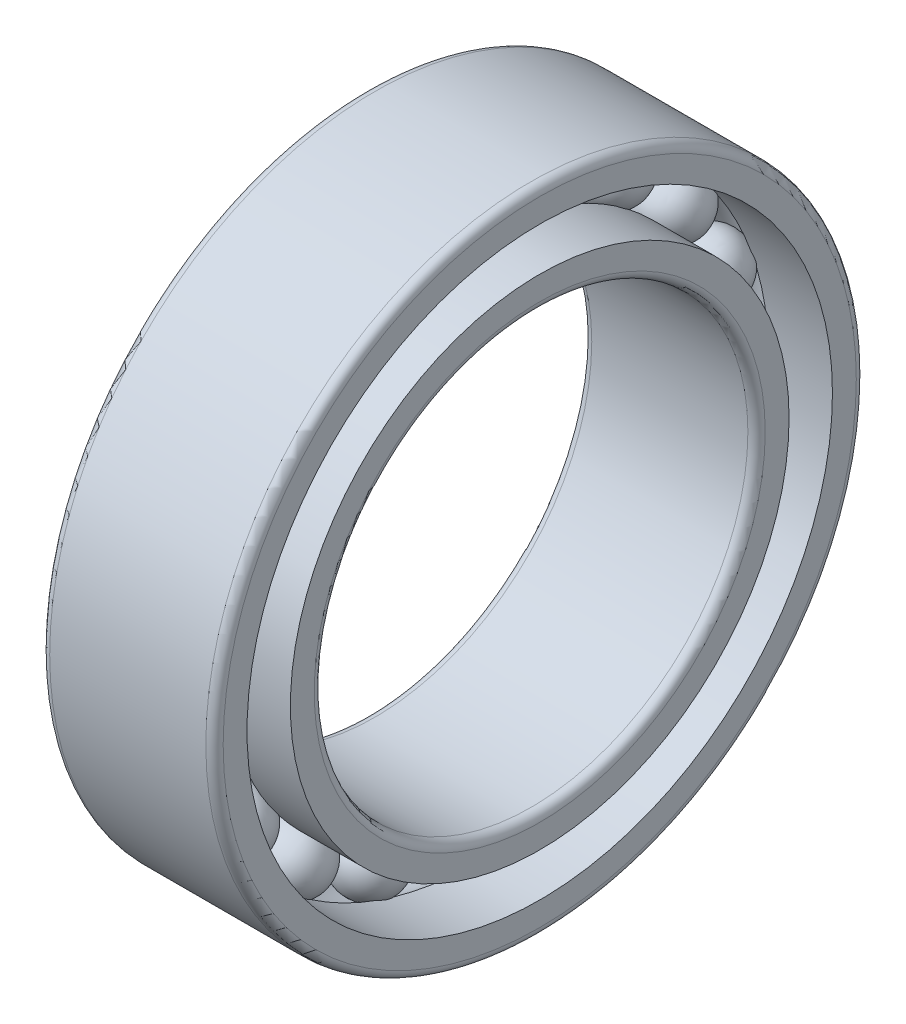
SolidWorks part; units mm, degrees
ref_plane "Plane1" through (0, 0, 0) normal (0, 0, 1) x (1, 0, 0)
ref_plane "Plane2" through (0, 0, 0) normal (0, 1, 0) x (1, 0, 0)
ref_plane "Plane3" through (0, 0, 0) normal (1, 0, 0) x (0, 0, -1)
sketch "Clipboard" plane through (0, 0, 0) normal (0, 0, 1) x (1, 0, 0)
  line L0 (-10, 0) -> (10, 0) construction
  line L1 (0, 0) -> (21.0122, -7.6478)
  line L2 (0, 0) -> (5.8731, 2.1376)
  line L3 (0, 0) -> (21.0122, -7.6478)
  line L4 (0, 0) -> (-22.3573, -0.3902)
  dimension "BallCLRad" = 6.25
sketch "CagSpiSke" plane through (0, 0, 0) normal (0, 0, 1) x (1, 0, 0)
  line L0 (0.075, 6.125) -> (0.075, 6.375)
  line L1 (0.075, 6.375) -> (-0.075, 6.375)
  line L2 (-0.075, 6.375) -> (-0.075, 6.125)
  line L3 (-0.075, 6.125) -> (0.075, 6.125)
  line L4 (-20.6375, 0) -> (20.6375, 0) construction
  line L5 (0, 0) -> (0, 23.7692) construction
  dimension "OD" = 12.75
  dimension "ID" = 12.25
revolve "CageSpine" add sketch "CagSpiSke" angle 0.001 about L4 reverse direction yes
ref_axis "Axis1" through (-50, 0, 0) along (1, 0, 0)
sketch "CagBalSke" plane through (0, 0, 0) normal (0, 0, 1) x (1, 0, 0)
  line L0 (-0.825, 6.25) -> (0.825, 6.25)
  line L1 (-1.905, 6.25) -> (1.905, 6.25) construction
  line L2 (-10, 0) -> (10, 0) construction
  line L3 (0, 0) -> (0, 24) construction
  arc A0 (0.825, 6.25) -> (-0.825, 6.25) centre (0, 6.25) cw
  dimension "BallCLRad" = 6.25
revolve "CageBall" [suppressed] add sketch "CagBalSke" angle 360 about L1 reverse direction yes
pattern_circular "CageBalls" [suppressed] count 20 every 18 about axis through (-50, 0, 0) along (1, 0, 0)
sketch "CagTrmODSke" plane through (0, 0, 0) normal (0, 0, 1) x (1, 0, 0)
  line L0 (0.826, 6.375) -> (0.826, 7.076)
  line L1 (0.826, 7.076) -> (-0.826, 7.076)
  line L2 (-0.826, 7.076) -> (-0.826, 6.375)
  line L3 (-0.826, 6.375) -> (0.826, 6.375)
  line L4 (-20.6375, 0) -> (20.6375, 0) construction
  line L5 (0, 0) -> (0, 25) construction
  dimension "Width" = 1.652
  dimension "ID" = 12.75
  dimension "OD" = 14.152
revolve "CageTrimOD" [suppressed] cut sketch "CagTrmODSke" angle 360 about L4 reverse direction yes
sketch "CagTrmIDSke" plane through (0, 0, 0) normal (0, 0, 1) x (1, 0, 0)
  line L0 (0.826, 5.426) -> (0.826, 6.125)
  line L1 (0.826, 6.125) -> (-0.826, 6.125)
  line L2 (-0.826, 6.125) -> (-0.826, 5.426)
  line L3 (-0.826, 5.426) -> (0.826, 5.426)
  line L4 (-20.6375, 0) -> (20.6375, 0) construction
  line L5 (0, 0) -> (0, 25) construction
  dimension "Width" = 1.652
  dimension "ID" = 10.852
  dimension "OD" = 12.25
revolve "CageTrimID" [suppressed] cut sketch "CagTrmIDSke" angle 360 about L4 reverse direction yes
sketch "BalSimSke" plane through (0, 0, 0) normal (0, 0, 1) x (1, 0, 0)
  line L0 (-10, 0) -> (10, 0) construction
  line L1 (-10, 6.25) -> (10, 6.25) construction
  line L2 (0, 0) -> (0, 23) construction
  circle A0 centre (0, 6.25) radius 0.75
  dimension "BallCLRad" = 6.25
  dimension "Ball_diameter" = 1.5
revolve "BallsSimplified" [suppressed] add sketch "BalSimSke" angle 360 about L0
sketch "BalDetSke" plane through (0, 0, 0) normal (0, 0, 1) x (1, 0, 0)
  line L0 (-0.75, 6.25) -> (0.75, 6.25)
  line L1 (-1.905, 6.25) -> (1.905, 6.25) construction
  line L2 (0, 0) -> (0, 25) construction
  arc A0 (0.75, 6.25) -> (-0.75, 6.25) centre (0, 6.25) cw
  dimension "BallCLRad" = 6.25
  dimension "Ball_diameter" = 1.5
revolve "BallDetailed" add sketch "BalDetSke" angle 360 about L1 reverse direction yes
sketch "InnRacSke" plane through (0, 0, 0) normal (0, 0, 1) x (1, 0, 0)
  line L0 (-0.525, 5.75) -> (-2, 5.75)
  line L1 (-2, 5.75) -> (-2, 5.2)
  line L2 (-1.8, 5) -> (1.8, 5)
  line L3 (2, 5.2) -> (2, 5.75)
  line L4 (2, 5.75) -> (0.525, 5.75)
  line L5 (-20.6375, 0) -> (20.6375, 0) construction
  line L6 (0, 0) -> (0, 30) construction
  arc A0 (-2, 5.2) -> (-1.8, 5) centre (-1.8, 5.2) ccw
  arc A1 (1.8, 5) -> (2, 5.2) centre (1.8, 5.2) ccw
  arc A2 (0.525, 5.75) -> (-0.525, 5.75) centre (0, 6.25) cw
  dimension "BallCLRad" = 6.25
  dimension "Fillet_radius" = 0.2
  dimension "Ball_diameter" = 1.45
  dimension "ID" = 10
  dimension "OD" = 11.5
  dimension "Width" = 4
revolve "InnerRace" add sketch "InnRacSke" angle 360 about L5 reverse direction yes
sketch "OutRacSke" plane through (0, 0, 0) normal (0, 0, 1) x (1, 0, 0)
  line L0 (-0.525, 6.75) -> (-2, 6.75)
  line L1 (-2, 6.75) -> (-2, 7.3)
  line L2 (-1.8, 7.5) -> (1.8, 7.5)
  line L3 (2, 7.3) -> (2, 6.75)
  line L4 (2, 6.75) -> (0.525, 6.75)
  line L5 (-20.6375, 0) -> (20.6375, 0) construction
  line L6 (0, 0) -> (0, 30) construction
  arc A0 (-2, 7.3) -> (-1.8, 7.5) centre (-1.8, 7.3) cw
  arc A1 (1.8, 7.5) -> (2, 7.3) centre (1.8, 7.3) cw
  arc A2 (0.525, 6.75) -> (-0.525, 6.75) centre (0, 6.25) ccw
  dimension "BallCLRad" = 6.25
  dimension "Fillet_radius" = 0.2
  dimension "Ball_diameter" = 1.45
  dimension "Width" = 4
revolve "OuterRace" add sketch "OutRacSke" angle 360 about L5 reverse direction yes
pattern_circular "BallsDetailed" count 20 every 18 about axis through (-50, 0, 0) along (1, 0, 0) of "BallDetailed"
equation "\"BallCLRad@Clipboard\" = ( \"OD@OutRacSke\" + \"ID@InnRacSke\" ) / 4"
equation "\"BallCLRad@BalSimSke\" = \"BallCLRad@Clipboard\""
equation "\"BallCLRad@BalDetSke\" = \"BallCLRad@Clipboard\""
equation "\"BallCLRad@InnRacSke\" = \"BallCLRad@Clipboard\""
equation "\"BallCLRad@OutRacSke\" = \"BallCLRad@Clipboard\""
equation "\"Ball_diameter@InnRacSke\" = \"Ball_diameter@BalDetSke\" - 0.05"
equation "\"Ball_diameter@OutRacSke\" = \"Ball_diameter@BalDetSke\" - 0.05"
equation "\"Ball_diameter@BalSimSke\" = \"Ball_diameter@BalDetSke\""
equation "\"Fillet_radius@OutRacSke\" = \"Fillet_radius@InnRacSke\""
equation "\"Max_count@Clipboard\" = int( 3.14159265 / atn(( \"Ball_diameter@BalDetSke\" / 2) / sqr( \"BallCLRad@Clipboard\"  *  \"BallCLRad@Clipboard\" - ( \"Ball_diameter@BalDetSke\" / 2) *  ( \"Ball_diameter@BalDetSke\" / 2))))"
equation "\"Max_count@Clipboard\" = ((sgn( \"Max_count@Clipboard\" - \"Count@Clipboard\" )-1)*( \"Max_count@Clipboard\" - \"Count@Clipboard\" ))/-2+ \"Count@Clipboard\""
equation "\"Count@BallsDetailed\" = int( \"Show_count@Clipboard\" ) "
equation "\"Count@BallsDetailed\" = ((sgn( \"Count@BallsDetailed\" - \"Max_count@Clipboard\" )-1)*( \"Count@BallsDetailed\" - \"Max_count@Clipboard\" ))/-2+ \"Max_count@Clipboard\""
equation "\"Count@BallsDetailed\" = ((sgn( \"Count@BallsDetailed\" - \"Min_count@Clipboard\" )+1)*( \"Count@BallsDetailed\" - \"Min_count@Clipboard\"))/2 +\"Min_count@Clipboard\""
equation "\"Angle@BallsDetailed\" = 360.0 / \"Max_count@Clipboard\""
equation "\"BallCLRad@CagBalSke\" = \"BallCLRad@Clipboard\""
equation "\"Count@CageBalls\" = \"Count@BallsDetailed\""
equation "\"Angle@CageBalls\" = \"Angle@BallsDetailed\""
equation "\"Angle@CageSpine\" =  \"Angle@CageBalls\" * ( \"Count@CageBalls\" -1 + int( \"Count@CageBalls\" / \"Max_count@Clipboard\" ) )  + 0.001 -  int( \"Count@CageBalls\" / \"Max_count@Clipboard\" ) * 0.001"
equation "\"Angle@CageSpine\" =  \"Angle@CageSpine\" * int( \"Min_count@Clipboard\" / 2) + int(1 / \"Min_count@Clipboard\")  * 0.001"
equation "\"CageWallOD@CagBalSke\" =  \"Ball_diameter@BalDetSke\" * 1.1"
equation "\"Thickness@CagSpiSke\" =  \"Ball_diameter@BalDetSke\" * 0.1"
equation "\"OD@CagTrmODSke\" = \"BallCLRad@Clipboard\" * 2 + \"CageWallOD@CagBalSke\" + 0.002"
equation "\"ID@CagTrmODSke\" = \"BallCLRad@Clipboard\" * 2 + \"Ball_diameter@BalDetSke\" / 6"
equation "\"OD@CagTrmIDSke\" = \"BallCLRad@Clipboard\" * 2 - \"Ball_diameter@BalDetSke\" / 6"
equation "\"ID@CagTrmIDSke\" = \"BallCLRad@Clipboard\" * 2 - \"CageWallOD@CagBalSke\" + 0.002"
equation "\"OD@CagSpiSke\" = \"ID@CagTrmODSke\""
equation "\"ID@CagSpiSke\" = \"OD@CagTrmIDSke\""
equation "\"Width@CagTrmODSke\" = \"CageWallOD@CagBalSke\" + 0.002"
equation "\"Width@CagTrmIDSke\" = \"CageWallOD@CagBalSke\" + 0.002"
